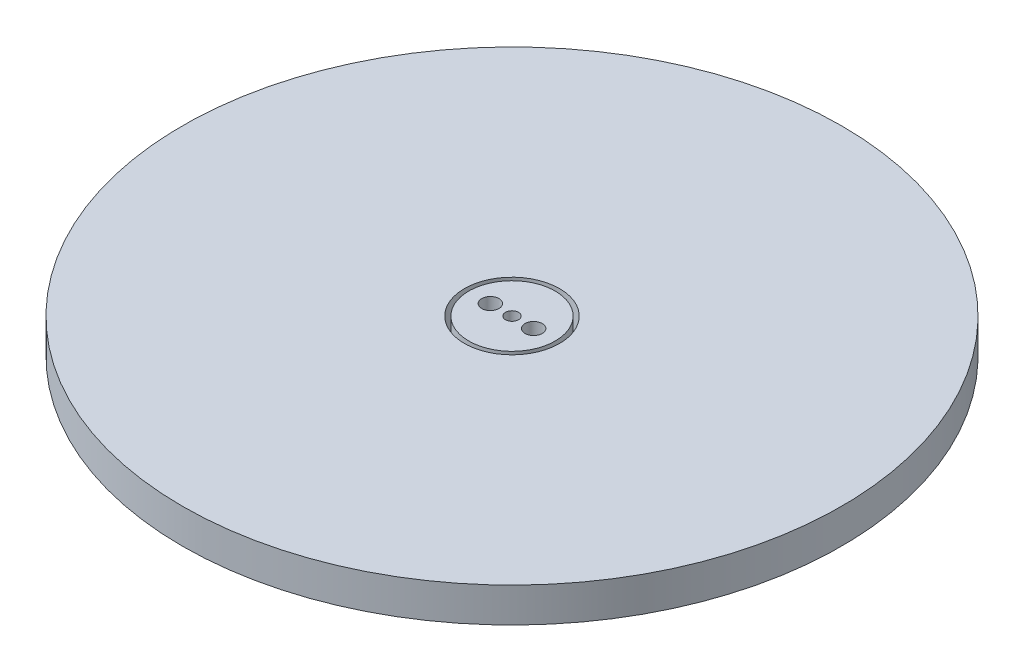
SolidWorks part; units mm, degrees
ref_plane "Front Plane" through (0, 0, 0) normal (0, 0, 1) x (1, 0, 0)
ref_plane "Top Plane" through (0, 0, 0) normal (0, 1, 0) x (1, 0, 0)
ref_plane "Right Plane" through (0, 0, 0) normal (1, 0, 0) x (0, 0, -1)
sketch "Sketch1" plane through (0, 0, 0) normal (0, 1, 0) x (1, 0, 0)
  line L0 (-2.5, 0) -> (2.5, 0) construction
  line L1 (0, 5) -> (0, -5) construction
  circle A1 centre (0, 0) radius 0.75
  circle A2 centre (-2.5, 0) radius 1
  circle A4 centre (0, 0) radius 5
  circle A5 centre (2.5, 0) radius 1
  dimension "D1" = 2.5
  dimension "D2" = 1.5
  dimension "D3" = 2
  dimension "D4" = 10
extrude "Boss-Extrude1" add sketch "Sketch1" along normal mid plane 4
sketch "Sketch2" plane through (0, -2, 0) normal (0, -1, 0) x (1, 0, 0)
  circle A0 centre (0, 0) radius 38.1
  circle A4 centre (0, 0) radius 5.5
  circle A5 centre (0, 0) radius 5.5
  dimension "D2" = 76.2
  dimension "D1" = 0.5
extrude "Boss-Extrude2" add sketch "Sketch2" against normal up to surface (4 mm away) separate body up to face at (-2.5, 2, 1)
